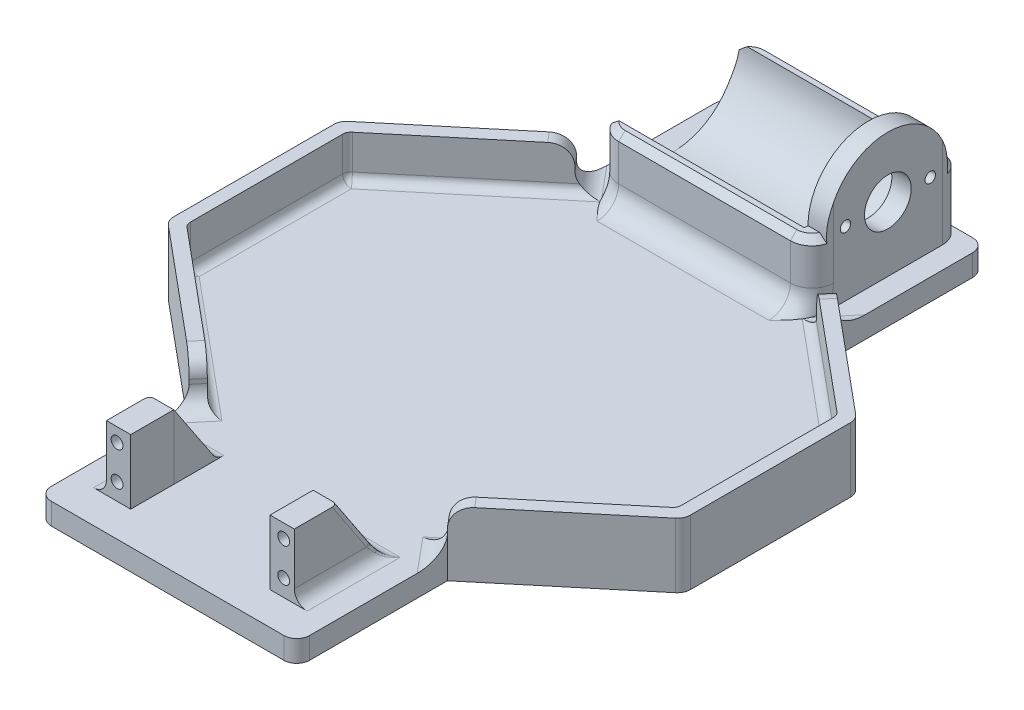
SolidWorks part; units mm, degrees
ref_plane "Front Plane" through (0, 0, 0) normal (0, 0, 1) x (1, 0, 0)
ref_plane "Top Plane" through (0, 0, 0) normal (0, 1, 0) x (1, 0, 0)
ref_plane "Right Plane" through (0, 0, 0) normal (1, 0, 0) x (0, 0, -1)
sketch "Sketch1" plane through (0, 0, 0) normal (0, 1, 0) x (1, 0, 0)
  line L0 (-34.29, 0) -> (34.29, 0)
  line L1 (0, 0) -> (0, 203.2) construction
  line L2 (-34.29, 203.2) -> (34.29, 203.2)
  line L3 (0, 101.6) -> (76.2, 101.6) construction
  line L4 (38.1, 199.39) -> (38.1, 158.75)
  line L5 (38.1, 158.75) -> (74.8291, 128.1424)
  line L6 (76.2, 125.2155) -> (76.2, 77.9845)
  line L7 (38.1, 44.45) -> (74.8291, 75.0576)
  line L8 (38.1, 3.81) -> (38.1, 44.45)
  line L9 (0, 0) -> (34.29, 0)
  line L10 (-38.1, 3.81) -> (-38.1, 44.45)
  line L11 (-38.1, 44.45) -> (-74.8291, 75.0576)
  line L12 (-76.2, 125.2155) -> (-76.2, 77.9845)
  line L13 (-38.1, 158.75) -> (-74.8291, 128.1424)
  line L14 (-38.1, 199.39) -> (-38.1, 158.75)
  arc A0 (38.1, 199.39) -> (34.29, 203.2) centre (34.29, 199.39) ccw
  arc A1 (76.2, 125.2155) -> (74.8291, 128.1424) centre (72.39, 125.2155) ccw
  arc A2 (76.2, 77.9845) -> (74.8291, 75.0576) centre (72.39, 77.9845) cw
  arc A3 (38.1, 3.81) -> (34.29, 0) centre (34.29, 3.81) cw
  arc A4 (-38.1, 3.81) -> (-34.29, 0) centre (-34.29, 3.81) ccw
  arc A5 (-76.2, 77.9845) -> (-74.8291, 75.0576) centre (-72.39, 77.9845) ccw
  arc A6 (-76.2, 125.2155) -> (-74.8291, 128.1424) centre (-72.39, 125.2155) cw
  arc A7 (-38.1, 199.39) -> (-34.29, 203.2) centre (-34.29, 199.39) cw
  point P14 (38.1, 203.2)
  point P17 (76.2, 127)
  point P20 (76.2, 76.2)
  dimension "D1" = 3.81
  dimension "D2" = 203.2
  dimension "D3" = 76.2
  dimension "D4" = 38.1
  dimension "D5" = 25.4
  dimension "D6" = 44.45
extrude "Boss-Extrude1" add sketch "Sketch1" along normal blind 6.35 contours A7 L14 L13 A6 L12 A5 L11 L10 A4 L0 A3 L8 L7 A2 L6 A1 L5 L4 A0 L2 region at (0, 0, -101.6)
sketch "Sketch2" plane through (0, 6.35, 0) normal (0, 1, 0) x (1, 0, 0)
  line L0 (0, 0) -> (0, 9.6774) construction
  line L1 (-27.6987, 9.6774) -> (-27.6987, 22.3774)
  line L2 (-20.5486, 9.6774) -> (-27.6987, 9.6774)
  line L3 (20.5486, 9.6774) -> (27.6987, 9.6774)
  line L4 (-27.6987, 22.3774) -> (-20.5486, 22.3774)
  line L5 (-20.5486, 22.3774) -> (-20.5486, 9.6774)
  line L6 (27.6987, 22.3774) -> (20.5486, 22.3774)
  line L7 (27.6987, 9.6774) -> (27.6987, 22.3774)
  line L8 (20.5486, 22.3774) -> (20.5486, 9.6774)
  point P6 (0, 9.6774)
  dimension "D1" = 9.6774
  dimension "D2" = 41.0972
  dimension "D4" = 12.7
extrude "Boss-Extrude2" add sketch "Sketch2" along normal blind 19.05 contours L6 L8 L3 L7 | L5 L2 L1 L4 region at (24.1236, 6.35, -16.0274)
sketch "Sketch3" plane through (-27.6987, 0, 0) normal (-1, 0, 0) x (0, 0, 1)
  line L0 (-22.3774, 25.4) -> (-35.0774, 6.35)
  line L1 (-3.81, 6.35) -> (-44.45, 6.35) construction
  line L2 (-35.0774, 6.35) -> (-22.3774, 6.35)
  line L3 (-22.3774, 6.35) -> (-22.3774, 25.4)
  dimension "D1" = 12.7
extrude "Boss-Extrude3" add sketch "Sketch3" against normal blind 7.1628
ref_plane "Plane1" through (0, 0, 0) normal (-1, 0, 0) x (0, 0, 1)
mirror "Mirror1" about plane through (0, 0, 0) normal (-1, 0, 0) of "Boss-Extrude3"
fillet "Fillet1" radius 3.81 4 edges at (27.6987, 6.35, -22.3774) (24.1173, 6.35, -35.0774) (-24.1173, 6.35, -35.0774) (-27.6987, 6.35, -22.3774)
sketch "Sketch4" plane through (0, 6.35, 0) normal (0, 1, 0) x (1, 0, 0)
  line L0 (-38.1, 158.75) -> (-74.8291, 128.1424)
  line L1 (-76.2, 125.2155) -> (-76.2, 77.9845) construction
  line L2 (-76.2, 125.2155) -> (-76.2, 77.9845)
  line L3 (-74.8291, 75.0576) -> (-38.1, 44.45)
  line L4 (-35.6609, 155.8231) -> (-72.39, 125.2155)
  line L5 (-72.39, 125.2155) -> (-72.39, 77.9845)
  line L6 (-72.39, 77.9845) -> (-35.6609, 47.3769)
  line L7 (-38.1, 44.45) -> (-35.6609, 47.3769)
  line L8 (-38.1, 158.75) -> (-35.6609, 155.8231)
  line L9 (0, 8.382) -> (0, -8.382) construction
  line L10 (35.6609, 155.8231) -> (72.39, 125.2155)
  line L11 (38.1, 158.75) -> (74.8291, 128.1424)
  line L12 (72.39, 125.2155) -> (72.39, 77.9845)
  line L13 (76.2, 125.2155) -> (76.2, 77.9845)
  line L14 (38.1, 44.45) -> (35.6609, 47.3769)
  line L15 (74.8291, 75.0576) -> (38.1, 44.45)
  line L16 (72.39, 77.9845) -> (35.6609, 47.3769)
  line L17 (38.1, 158.75) -> (35.6609, 155.8231)
  arc A0 (-74.8291, 128.1424) -> (-76.2, 125.2155) centre (-72.39, 125.2155) ccw
  arc A1 (-76.2, 77.9845) -> (-74.8291, 75.0576) centre (-72.39, 77.9845) ccw
  arc A2 (-72.39, 125.2155) -> (-72.39, 125.2155) centre (-72.39, 125.2155) ccw
  arc A3 (-72.39, 77.9845) -> (-72.39, 77.9845) centre (-72.39, 77.9845) ccw
  arc A4 (74.8291, 128.1424) -> (76.2, 125.2155) centre (72.39, 125.2155) cw
  arc A5 (76.2, 77.9845) -> (74.8291, 75.0576) centre (72.39, 77.9845) cw
  dimension "D1" = 3.81
extrude "Boss-Extrude4" add sketch "Sketch4" along normal blind 12.7
fillet "Fillet3" radius 5.715 8 edges at (36.8804, 6.35, -45.9135) (-36.8804, 6.35, -45.9135) (36.8804, 6.35, -157.2865) (-36.8804, 6.35, -157.2865) (36.8804, 19.05, -157.2865) (-36.8804, 19.05, -157.2865) (36.8804, 19.05, -45.9135) (-36.8804, 19.05, -45.9135)
sketch "Sketch6" plane through (0, 0, -9.6774) normal (0, 0, 1) x (1, 0, 0)
  line L0 (-34.29, 6.35) -> (34.29, 6.35) construction
  line L1 (-20.5359, 6.35) -> (-20.5359, 25.4) construction
  circle A0 centre (-24.5745, 11.3538) radius 1.7399
  circle A1 centre (-24.5745, 21.3614) radius 1.7399
  dimension "D4" = 3.4798
  dimension "D5" = 3.4798
  dimension "D1" = 5.0038
  dimension "D2" = 4.0386
  dimension "D3" = 15.0114
extrude "Cut-Extrude1" cut sketch "Sketch6" against normal blind 7.62
mirror "Mirror2" about plane through (0, 0, 0) normal (-1, 0, 0) of "Cut-Extrude1"
sketch "Sketch7" plane through (0, 6.35, 0) normal (0, 1, 0) x (1, 0, 0)
  line L0 (0, 203.2) -> (0, 158.3944) construction
  line L1 (-34.29, 203.2) -> (34.29, 203.2) construction
  line L3 (-31.6738, 158.3944) -> (31.6738, 158.3944)
  line L4 (-31.6738, 158.3944) -> (-31.6738, 203.2)
  line L5 (-31.6738, 203.2) -> (31.6738, 203.2)
  line L6 (31.6738, 158.3944) -> (31.6738, 203.2)
  line L7 (-31.6738, 158.3944) -> (31.6738, 203.2) construction
  line L8 (-31.6738, 203.2) -> (31.6738, 158.3944) construction
  point P5 (0, 180.7972)
  dimension "D1" = 44.8056
  dimension "D2" = 63.3476
extrude "Boss-Extrude5" add sketch "Sketch7" along normal blind 38.1
sketch "Sketch8" plane through (-31.6738, 0, 0) normal (-1, 0, 0) x (0, 0, 1)
  line L0 (-180.7972, 6.35) -> (-180.7972, 6.4897) construction
  line L1 (-161.8869, 25.4) -> (-158.3944, 25.4)
  line L2 (-203.2, 44.45) -> (-158.3944, 44.45) construction
  line L3 (-158.3944, 44.45) -> (-158.3944, 6.35) construction
  line L4 (-203.2, 44.45) -> (-158.3944, 44.45)
  line L5 (-203.2, 44.45) -> (-203.2, 25.4)
  line L6 (-203.2, 25.4) -> (-199.7075, 25.4)
  line L7 (-158.3944, 44.45) -> (-158.3944, 25.4)
  line L8 (-180.7972, 44.3103) -> (-180.7972, 44.45) construction
  arc A0 (-199.7075, 25.4) -> (-161.8869, 25.4) centre (-180.7972, 25.4) ccw
  dimension "D1" = 37.8206
extrude "Cut-Extrude2" cut sketch "Sketch8" against normal blind 57.6326
sketch "Sketch10" plane through (31.6738, 0, 0) normal (1, 0, 0) x (0, 0, -1)
  line L0 (180.7972, 6.35) -> (180.7972, 7.5184) construction
  line L4 (158.3944, 6.35) -> (203.2, 6.35) construction
  line L5 (203.2, 44.45) -> (203.2, 6.35) construction
  line L7 (158.3944, 44.45) -> (203.2, 44.45)
  line L8 (158.3944, 44.45) -> (158.3944, 25.4)
  line L9 (158.3944, 25.4) -> (162.941, 25.4)
  line L10 (203.2, 44.45) -> (203.2, 25.4)
  line L11 (198.6534, 25.4) -> (203.2, 25.4)
  arc A0 (198.6534, 25.4) -> (162.941, 25.4) centre (180.7972, 25.3746) ccw
  dimension "D2" = 35.7124
  dimension "D1" = 19.0246
extrude "Cut-Extrude3" cut sketch "Sketch10" against normal up to next
fillet "Fillet4" radius 6.35 1 edges at (0, 6.35, -158.3944)
fillet "Fillet5" radius 6.35 6 edges at (-31.6738, 8.2099, -156.5345) (31.6738, 8.2099, -156.5345) (-31.6738, 15.875, -203.2) (-31.6738, 19.05, -158.3944) (31.6738, 15.875, -203.2) (31.6738, 19.05, -158.3944)
chamfer "Chamfer1" distance 1.905 angle 45 6 edges at (29.1232, 25.4, -159.6565) (-28.6538, 25.4, -159.3376) (0, 25.4, -158.3944) (29.1232, 25.4, -201.9379) (-28.6538, 25.4, -202.2568) (0, 25.4, -203.2)
sketch "Sketch11" plane through (31.6738, 0, 0) normal (1, 0, 0) x (0, 0, -1)
  line L0 (180.7972, 43.2308) -> (180.7972, 6.35) construction
  line L1 (163.0429, 6.35) -> (196.85, 6.35) construction
  line L2 (168.3004, 25.4) -> (193.294, 25.4) construction
  arc A0 (196.85, 33.1945) -> (164.7444, 33.1945) centre (180.7972, 25.3746) ccw construction
  circle A1 centre (180.7972, 25.4) radius 6.8961
  circle A2 centre (168.3004, 25.4) radius 1.5494
  circle A3 centre (193.294, 25.4) radius 1.5494
  point P12 (180.7972, 25.4)
  dimension "D2" = 13.7922
  dimension "D4" = 3.0988
  dimension "D1" = 19.05
  dimension "D3" = 24.9936
extrude "Cut-Extrude4" cut sketch "Sketch11" against normal up to next contours A1 | A3 | A2 region at (31.6738, 25.4, -180.7972) region at (31.6738, 25.4, -193.294)
fillet "Fillet6" radius 2.54 10 edges at (51.8303, 6.35, -142.3486) (72.39, 12.7, -125.2155) (51.8303, 6.35, -60.8514) (72.39, 12.7, -77.9845) (72.39, 6.35, -101.6) (-51.8303, 6.35, -142.3486) (-72.39, 6.35, -101.6) (-51.8303, 6.35, -60.8514) (-72.39, 12.7, -77.9845) (-72.39, 12.7, -125.2155)
fillet "Fillet8" radius 1.27 6 edges at (-29.7109, 6.8008, -35.3187) (-27.8622, 9.0559, -33.2735) (29.7109, 6.8008, -35.3187) (27.8622, 9.0559, -33.2735) (-27.6987, 17.78, -27.4574) (27.6987, 17.78, -27.4574)
